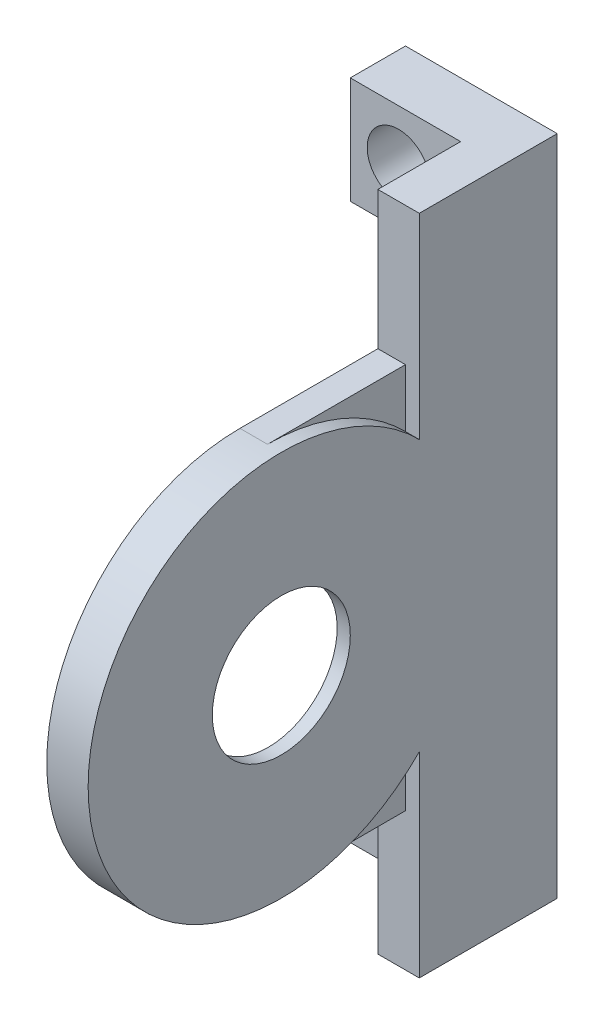
SolidWorks part; units mm, degrees
material "사용자정의 플라스틱"
ref_plane "정면" through (0, 0, 0) normal (0, 0, 1) x (1, 0, 0)
ref_plane "윗면" through (0, 0, 0) normal (0, 1, 0) x (1, 0, 0)
ref_plane "우측면" through (0, 0, 0) normal (1, 0, 0) x (0, 0, -1)
sketch "스케치1" plane through (0, 0, 0) normal (0, 0, 1) x (1, 0, 0)
  line L1 (-10, 28) -> (10, 28)
  line L2 (-10, 28) -> (-10, -28)
  line L3 (-10, -28) -> (10, -28)
  line L4 (10, 28) -> (10, -28)
  line L5 (-10, 28) -> (10, -28) construction
  line L6 (-10, -28) -> (10, 28) construction
  point P0 (0, 0)
  dimension "D1" = 20
  dimension "56" = 56
extrude "보스-돌출1" add sketch "스케치1" along normal blind 8
sketch "스케치2" plane through (0, 0, 8) normal (0, 0, 1) x (1, 0, 0)
  line L0 (-10, -28) -> (10, -28) construction
  line L1 (10, 28) -> (6, 28)
  line L2 (10, 28) -> (10, -28)
  line L3 (10, -28) -> (6, -28)
  line L4 (6, 28) -> (6, -28)
  dimension "D1" = 4
extrude "보스-돌출2" add sketch "스케치2" along normal blind 60
fillet "필렛1" radius 28 2 edges at (8, 28, 68) (8, -28, 68)
sketch "스케치5" plane through (10, 0, 0) normal (1, 0, 0) x (0, 0, -1)
  circle A0 centre (-40, 0) radius 28
  arc A1 (-68, 0) -> (-40, -28) centre (-40, 0) ccw construction
  dimension "D1" = 0
  dimension "D2" = 0
extrude "보스-돌출3" add sketch "스케치5" along normal blind 2
sketch "스케치4" plane through (6, 0, 0) normal (-1, 0, 0) x (0, 0, 1)
  line L1 (35, 24) -> (45, 24)
  line L2 (35, 24) -> (35, 16)
  line L3 (35, 16) -> (45, 16)
  line L4 (45, 24) -> (45, 16)
  line L5 (35, 24) -> (45, 16) construction
  line L6 (35, 16) -> (45, 24) construction
  line L7 (35, -16) -> (45, -16)
  line L8 (35, -16) -> (35, -24)
  line L9 (35, -24) -> (45, -24)
  line L10 (45, -16) -> (45, -24)
  line L11 (35, -16) -> (45, -24) construction
  line L12 (35, -24) -> (45, -16) construction
  circle A0 centre (40, 0) radius 20
  arc A1 (40, -28) -> (68, 0) centre (40, 0) ccw construction
  point P5 (40, 20)
  point P10 (40, -20)
  dimension "D2" = 40
  dimension "D1" = 0
  dimension "D3" = 8
  dimension "D4" = 10
  dimension "D5" = 10
  dimension "D6" = 8
extrude "컷-돌출2" cut sketch "스케치4" against normal blind 4.1 contours L10 A0 L4 L3 L2 L8 L7 | A0 L8 L9 L10 | L8 A0 L10 L7 | A0 L4 L1 L2 | L4 A0 L2 L3 region at (6, 21.8906, 40) region at (6, 17.8995, 40) region at (6, 0, 40) region at (6, -21.8906, 40) region at (6, -17.8995, 40)
sketch "스케치6" plane through (10, 0, 0) normal (1, 0, 0) x (0, 0, -1)
  line L0 (-40, -28) -> (0, -28) construction
  line L1 (0, 28) -> (-20, 28)
  line L2 (0, 28) -> (0, -28)
  line L3 (0, -28) -> (-20, -28)
  line L4 (-20, 28) -> (-20, -28)
extrude "보스-돌출4" add sketch "스케치6" along normal blind 2
sketch "스케치7" plane through (10.1, 0, 0) normal (-1, 0, 0) x (0, 0, 1)
  circle A0 centre (40, 0) radius 10
  circle A1 centre (40, 0) radius 20 construction
  dimension "D1" = 0
  dimension "D2" = 20
extrude "컷-돌출3" cut sketch "스케치7" against normal blind 2
sketch "스케치8" plane through (0, 28, 0) normal (0, 1, 0) x (1, 0, 0)
  line L0 (-10, -8) -> (-10, 0)
  line L1 (-10, 0) -> (12, 0)
  line L2 (12, 0) -> (12, -20)
  line L3 (12, -20) -> (6, -20)
  line L4 (6, -40) -> (6, -8) construction
  line L5 (6, -20) -> (6, -8)
  line L6 (6, -8) -> (-10, -8)
  line L7 (6, -8) -> (-10, -8) construction
  line L8 (-10, -8) -> (-10, 0) construction
extrude "보스-돌출5" add sketch "스케치8" along normal blind 20
mirror "대칭 복사1" about plane through (0, 0, 0) normal (0, 1, 0) of "보스-돌출5"
sketch "스케치3" plane through (0, 0, 8) normal (0, 0, 1) x (1, 0, 0)
  line L0 (-10, 48) -> (-10, -48) construction
  line L1 (-10, -28) -> (6, -28) construction
  line L2 (6, 28) -> (-10, 28) construction
  circle A0 centre (-3, -40.5) radius 4.55
  circle A1 centre (-3, 40.5) radius 4.55
  dimension "D1" = 9.1
  dimension "D2" = 9.1
  dimension "D3" = 12.5
  dimension "D4" = 12.5
  dimension "D5" = 7
  dimension "D6" = 7
extrude "컷-돌출1" cut sketch "스케치3" against normal blind 60
sketch "스케치9" plane through (0, 0, 8) normal (0, 0, 1) x (1, 0, 0)
  line L0 (-10, 48) -> (-10, -48) construction
  line L1 (5, 32.5) -> (-10, 32.5)
  line L2 (5, 32.5) -> (5, -32.5)
  line L3 (5, -32.5) -> (-10, -32.5)
  line L4 (-10, 32.5) -> (-10, -32.5)
  line L5 (5, 32.5) -> (-10, -32.5) construction
  line L6 (5, -32.5) -> (-10, 32.5) construction
  point P0 (-2.5, 0)
  dimension "D1" = 65
  dimension "D2" = 0
  dimension "D3" = 15
extrude "컷-돌출4" cut sketch "스케치9" against normal through all
